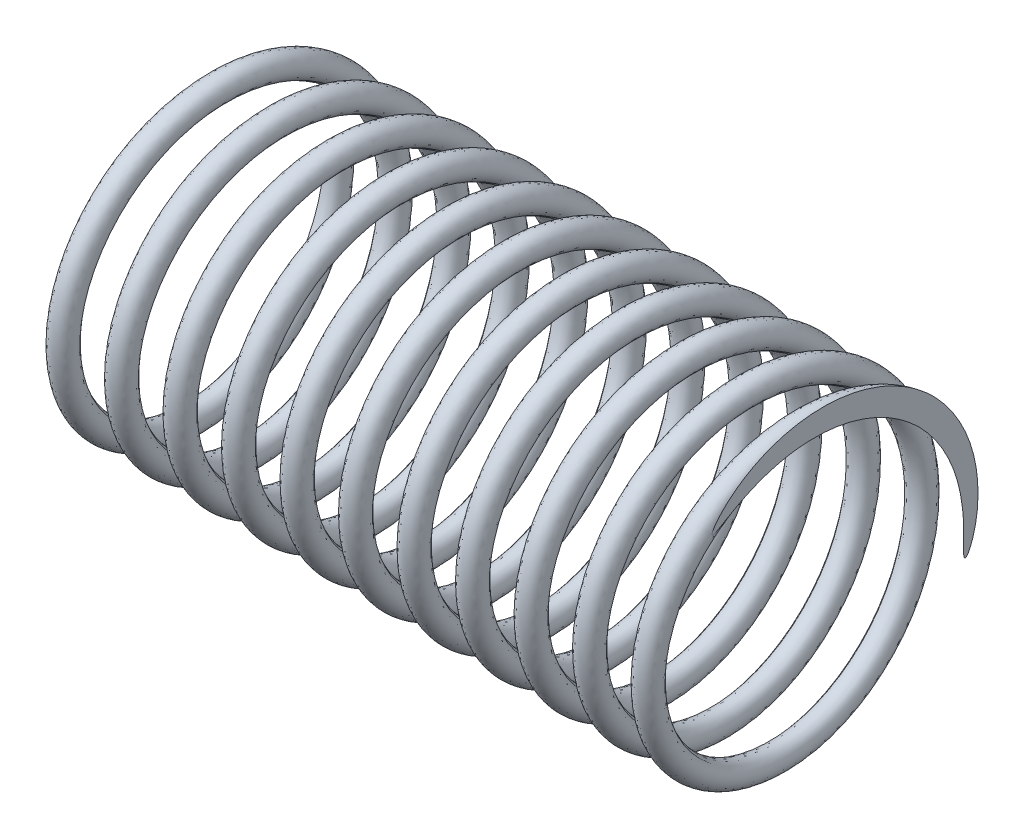
SolidWorks part; units mm, degrees
material "SPRING STEEL ASTM A 229"
ref_plane "Front Plane" through (0, 0, 0) normal (0, 0, 1) x (1, 0, 0)
ref_plane "Top Plane" through (0, 0, 0) normal (0, 1, 0) x (1, 0, 0)
ref_plane "Right Plane" through (0, 0, 0) normal (1, 0, 0) x (0, 0, -1)
sketch "Sketch1" plane through (0, 0, 0) normal (1, 0, 0) x (0, 0, -1)
  circle A0 centre (0, 0) radius 3.1
  dimension "D1" = 6.2
curve "Helix/Spiral1" pitch 1.2 height 26 radius 3.1 left hand yes centre (0, 0, 0) axis (1, 0, 0) start towards (0, 0, -1)
sketch "Sketch2" plane through (0, 0, 0) normal (0, 1, 0) x (1, 0, 0)
  circle A0 centre (0, 3.1) radius 0.25
  spline S0 degree 3 poles (0, 3.1) (0.0249, 3.1) (0.0752, 2.938) (0.1503, 2.2459) (0.2254, 1.2106) (0.3006, -0.0096) (0.3757, -1.2284) (0.4509, -2.2595) (0.526, -2.9453) (0.6012, -3.181) (0.6763, -2.9305) (0.7514, -2.2322) (0.8266, -1.1928) (0.9017, 0.0289) (0.9769, 1.2462) (1.052, 2.273) (1.1272, 2.9525) (1.2023, 3.1808) (1.2775, 2.923) (1.3526, 2.2185) (1.4277, 1.1749) (1.5029, -0.0481) (1.578, -1.2639) (1.6532, -2.2865) (1.7283, -2.9596) (1.8035, -3.1805) (1.8786, -2.9153) (1.9538, -2.2046) (2.0289, -1.157) (2.104, 0.0674) (2.1792, 1.2815) (2.2543, 2.2998) (2.3295, 2.9666) (2.4046, 3.1801) (2.4798, 2.9076) (2.5549, 2.1907) (2.6301, 1.1391) (2.7052, -0.0866) (2.7803, -1.2991) (2.8555, -2.3131) (2.9306, -2.9735) (3.0058, -3.1796) (3.0809, -2.8997) (3.1561, -2.1767) (3.2312, -1.1211) (3.3064, 0.1059) (3.3815, 1.3167) (3.4566, 2.3262) (3.5318, 2.9803) (3.6069, 3.1789) (3.6821, 2.8917) (3.7572, 2.1626) (3.8324, 1.103) (3.9075, -0.1251) (3.9827, -1.3342) (4.0578, -2.3393) (4.1329, -2.987) (4.2081, -3.1782) (4.2832, -2.8837) (4.3584, -2.1485) (4.4335, -1.085) (4.5087, 0.1444) (4.5838, 1.3516) (4.659, 2.3523) (4.7341, 2.9935) (4.8092, 3.1773) (4.8844, 2.8755) (4.9595, 2.1342) (5.0347, 1.0668) (5.1098, -0.1636) (5.185, -1.369) (5.2601, -2.3652) (5.3353, -3) (5.4104, -3.1763) (5.4855, -2.8672) (5.5607, -2.1199) (5.6358, -1.0487) (5.711, 0.1828) (5.7861, 1.3864) (5.8613, 2.3781) (5.9364, 3.0064) (6.0116, 3.1752) (6.0867, 2.8588) (6.1618, 2.1055) (6.237, 1.0305) (6.3121, -0.202) (6.3873, -1.4037) (6.4624, -2.3908) (6.5376, -3.0126) (6.6127, -3.174) (6.6879, -2.8503) (6.763, -2.0911) (6.8382, -1.0122) (6.9133, 0.2213) (6.9884, 1.4209) (7.0636, 2.4035) (7.1387, 3.0187) (7.2139, 3.1726) (7.289, 2.8417) (7.3642, 2.0765) (7.4393, 0.994) (7.5145, -0.2405) (7.5896, -1.4381) (7.6647, -2.4161) (7.7399, -3.0247) (7.815, -3.1712) (7.8902, -2.833) (7.9653, -2.0619) (8.0405, -0.9757) (8.1156, 0.2597) (8.1908, 1.4553) (8.2659, 2.4285) (8.341, 3.0306) (8.4162, 3.1696) (8.4913, 2.8242) (8.5665, 2.0472) (8.6416, 0.9573) (8.7168, -0.2788) (8.7919, -1.4724) (8.8671, -2.4409) (8.9422, -3.0364) (9.0173, -3.1679) (9.0925, -2.8153) (9.1676, -2.0324) (9.2428, -0.9389) (9.3179, 0.298) (9.3931, 1.4894) (9.4682, 2.4532) (9.5434, 3.0421) (9.6185, 3.1661) (9.6936, 2.8063) (9.7688, 2.0176) (9.8439, 0.9205) (9.9191, -0.3172) (9.9942, -1.5064) (10.0694, -2.4654) (10.1445, -3.0477) (10.2197, -3.1642) (10.2948, -2.7971) (10.3699, -2.0026) (10.4451, -0.9021) (10.5202, 0.3363) (10.5954, 1.5233) (10.6705, 2.4776) (10.7457, 3.0532) (10.8208, 3.1622) (10.896, 2.7879) (10.9711, 1.9876) (11.0462, 0.8836) (11.1214, -0.3555) (11.1965, -1.5402) (11.2717, -2.4896) (11.3468, -3.0585) (11.422, -3.16) (11.4971, -2.7786) (11.5723, -1.9726) (11.6474, -0.8651) (11.7225, 0.3746) (11.7977, 1.557) (11.8728, 2.5015) (11.948, 3.0637) (12.0231, 3.1577) (12.0983, 2.7692) (12.1734, 1.9574) (12.2486, 0.8465) (12.3237, -0.3937) (12.3988, -1.5738) (12.474, -2.5134) (12.5491, -3.0689) (12.6243, -3.1554) (12.6994, -2.7596) (12.7746, -1.9422) (12.8497, -0.828) (12.9249, 0.4128) (13, 1.5905) (13.0751, 2.5251) (13.1503, 3.0739) (13.2254, 3.1529) (13.3006, 2.75) (13.3757, 1.9269) (13.4509, 0.8094) (13.526, -0.4319) (13.6012, -1.6072) (13.6763, -2.5368) (13.7514, -3.0788) (13.8266, -3.1502) (13.9017, -2.7403) (13.9769, -1.9116) (14.052, -0.7907) (14.1272, 0.451) (14.2023, 1.6237) (14.2775, 2.5484) (14.3526, 3.0836) (14.4277, 3.1475) (14.5029, 2.7305) (14.578, 1.8961) (14.6532, 0.772) (14.7283, -0.47) (14.8035, -1.6403) (14.8786, -2.5599) (14.9538, -3.0882) (15.0289, -3.1447) (15.104, -2.7205) (15.1792, -1.8806) (15.2543, -0.7534) (15.3295, 0.4891) (15.4046, 1.6567) (15.4798, 2.5712) (15.5549, 3.0928) (15.6301, 3.1417) (15.7052, 2.7105) (15.7803, 1.8651) (15.8555, 0.7346) (15.9306, -0.5081) (16.0058, -1.6731) (16.0809, -2.5825) (16.1561, -3.0972) (16.2312, -3.1386) (16.3064, -2.7004) (16.3815, -1.8494) (16.4566, -0.7159) (16.5318, 0.5271) (16.6069, 1.6895) (16.6821, 2.5937) (16.7572, 3.1016) (16.8324, 3.1354) (16.9075, 2.6901) (16.9827, 1.8337) (17.0578, 0.6971) (17.1329, -0.5461) (17.2081, -1.7058) (17.2832, -2.6048) (17.3584, -3.1058) (17.4335, -3.1321) (17.5087, -2.6798) (17.5838, -1.818) (17.659, -0.6783) (17.7341, 0.565) (17.8092, 1.722) (17.8844, 2.6158) (17.9595, 3.1099) (18.0347, 3.1287) (18.1098, 2.6694) (18.185, 1.8021) (18.2601, 0.6595) (18.3353, -0.584) (18.4104, -1.7382) (18.4855, -2.6267) (18.5607, -3.1139) (18.6358, -3.1252) (18.711, -2.6589) (18.7861, -1.7862) (18.8613, -0.6406) (18.9364, 0.6029) (19.0116, 1.7543) (19.0867, 2.6375) (19.1618, 3.1178) (19.237, 3.1215) (19.3121, 2.6483) (19.3873, 1.7703) (19.4624, 0.6218) (19.5376, -0.6218) (19.6127, -1.7703) (19.6879, -2.6483) (19.763, -3.1215) (19.8382, -3.1178) (19.9133, -2.6375) (19.9884, -1.7543) (20.0636, -0.6029) (20.1387, 0.6406) (20.2139, 1.7862) (20.289, 2.6589) (20.3642, 3.1252) (20.4393, 3.1139) (20.5145, 2.6267) (20.5896, 1.7382) (20.6647, 0.584) (20.7399, -0.6595) (20.815, -1.8021) (20.8902, -2.6694) (20.9653, -3.1287) (21.0405, -3.1099) (21.1156, -2.6158) (21.1908, -1.722) (21.2659, -0.565) (21.341, 0.6783) (21.4162, 1.818) (21.4913, 2.6798) (21.5665, 3.1321) (21.6416, 3.1058) (21.7168, 2.6048) (21.7919, 1.7058) (21.8671, 0.5461) (21.9422, -0.6971) (22.0173, -1.8337) (22.0925, -2.6901) (22.1676, -3.1354) (22.2428, -3.1016) (22.3179, -2.5937) (22.3931, -1.6895) (22.4682, -0.5271) (22.5434, 0.7159) (22.6185, 1.8494) (22.6936, 2.7004) (22.7688, 3.1386) (22.8439, 3.0972) (22.9191, 2.5825) (22.9942, 1.6731) (23.0694, 0.5081) (23.1445, -0.7346) (23.2197, -1.8651) (23.2948, -2.7105) (23.3699, -3.1417) (23.4451, -3.0928) (23.5202, -2.5712) (23.5954, -1.6567) (23.6705, -0.4891) (23.7457, 0.7534) (23.8208, 1.8806) (23.896, 2.7205) (23.9711, 3.1447) (24.0462, 3.0882) (24.1214, 2.5599) (24.1965, 1.6403) (24.2717, 0.47) (24.3468, -0.772) (24.422, -1.8961) (24.4971, -2.7305) (24.5723, -3.1475) (24.6474, -3.0836) (24.7225, -2.5484) (24.7977, -1.6237) (24.8728, -0.451) (24.948, 0.7907) (25.0231, 1.9116) (25.0983, 2.7403) (25.1734, 3.1502) (25.2486, 3.0788) (25.3237, 2.5368) (25.3988, 1.6072) (25.474, 0.4319) (25.5491, -0.8093) (25.6243, -1.9269) (25.6994, -2.75) (25.7746, -3.1529) (25.8497, -3.0736) (25.9248, -2.5262) (25.9751, -1.8998) (26, -1.55) knots 0 0 0 0 0.00289 0.00578 0.008671 0.011561 0.014451 0.017341 0.020231 0.023121 0.026012 0.028902 0.031792 0.034682 0.037572 0.040462 0.043353 0.046243 0.049133 0.052023 0.054913 0.057803 0.060694 0.063584 0.066474 0.069364 0.072254 0.075145 0.078035 0.080925 0.083815 0.086705 0.089595 0.092486 0.095376 0.098266 0.101156 0.104046 0.106936 0.109827 0.112717 0.115607 0.118497 0.121387 0.124277 0.127168 0.130058 0.132948 0.135838 0.138728 0.141618 0.144509 0.147399 0.150289 0.153179 0.156069 0.15896 0.16185 0.16474 0.16763 0.17052 0.17341 0.176301 0.179191 0.182081 0.184971 0.187861 0.190751 0.193642 0.196532 0.199422 0.202312 0.205202 0.208092 0.210983 0.213873 0.216763 0.219653 0.222543 0.225434 0.228324 0.231214 0.234104 0.236994 0.239884 0.242775 0.245665 0.248555 0.251445 0.254335 0.257225 0.260116 0.263006 0.265896 0.268786 0.271676 0.274566 0.277457 0.280347 0.283237 0.286127 0.289017 0.291908 0.294798 0.297688 0.300578 0.303468 0.306358 0.309249 0.312139 0.315029 0.317919 0.320809 0.323699 0.32659 0.32948 0.33237 0.33526 0.33815 0.34104 0.343931 0.346821 0.349711 0.352601 0.355491 0.358382 0.361272 0.364162 0.367052 0.369942 0.372832 0.375723 0.378613 0.381503 0.384393 0.387283 0.390173 0.393064 0.395954 0.398844 0.401734 0.404624 0.407514 0.410405 0.413295 0.416185 0.419075 0.421965 0.424855 0.427746 0.430636 0.433526 0.436416 0.439306 0.442197 0.445087 0.447977 0.450867 0.453757 0.456647 0.459538 0.462428 0.465318 0.468208 0.471098 0.473988 0.476879 0.479769 0.482659 0.485549 0.488439 0.491329 0.49422 0.49711 0.5 0.50289 0.50578 0.508671 0.511561 0.514451 0.517341 0.520231 0.523121 0.526012 0.528902 0.531792 0.534682 0.537572 0.540462 0.543353 0.546243 0.549133 0.552023 0.554913 0.557803 0.560694 0.563584 0.566474 0.569364 0.572254 0.575145 0.578035 0.580925 0.583815 0.586705 0.589595 0.592486 0.595376 0.598266 0.601156 0.604046 0.606936 0.609827 0.612717 0.615607 0.618497 0.621387 0.624277 0.627168 0.630058 0.632948 0.635838 0.638728 0.641618 0.644509 0.647399 0.650289 0.653179 0.656069 0.65896 0.66185 0.66474 0.66763 0.67052 0.67341 0.676301 0.679191 0.682081 0.684971 0.687861 0.690751 0.693642 0.696532 0.699422 0.702312 0.705202 0.708092 0.710983 0.713873 0.716763 0.719653 0.722543 0.725434 0.728324 0.731214 0.734104 0.736994 0.739884 0.742775 0.745665 0.748555 0.751445 0.754335 0.757225 0.760116 0.763006 0.765896 0.768786 0.771676 0.774566 0.777457 0.780347 0.783237 0.786127 0.789017 0.791908 0.794798 0.797688 0.800578 0.803468 0.806358 0.809249 0.812139 0.815029 0.817919 0.820809 0.823699 0.82659 0.82948 0.83237 0.83526 0.83815 0.84104 0.843931 0.846821 0.849711 0.852601 0.855491 0.858382 0.861272 0.864162 0.867052 0.869942 0.872832 0.875723 0.878613 0.881503 0.884393 0.887283 0.890173 0.893064 0.895954 0.898844 0.901734 0.904624 0.907514 0.910405 0.913295 0.916185 0.919075 0.921965 0.924855 0.927746 0.930636 0.933526 0.936416 0.939306 0.942197 0.945087 0.947977 0.950867 0.953757 0.956647 0.959538 0.962428 0.965318 0.968208 0.971098 0.973988 0.976879 0.979769 0.982659 0.985549 0.988439 0.991329 0.99422 0.99711 1 1 1 1 construction
  dimension "D1" = 0.5
sweep "Sweep1" add profiles "Sketch2" path "Helix/Spiral1"
sketch "Sketch3" plane through (0, 0, 0) normal (0, 0, 1) x (1, 0, 0)
  line L0 (0, 0) -> (28.1754, 0) construction
  line L1 (58, 6.4802) -> (13, 6.4802)
  line L2 (58, 6.4802) -> (58, -6.4802)
  line L3 (58, -6.4802) -> (13, -6.4802)
  line L4 (13, 6.4802) -> (13, -6.4802)
  line L5 (0, 4.7829) -> (-1.4284, 4.7829)
  line L6 (0, 4.7829) -> (0, -6.4802)
  line L7 (0, -6.4802) -> (-1.4284, -6.4802)
  line L8 (-1.4284, 4.7829) -> (-1.4284, -6.4802)
  dimension "D1" = 11.2631
  dimension "D2" = 1.4284
  dimension "D3" = 4.7829
  dimension "D4" = 45
  dimension "D5" = 13
  dimension "D6" = 12.9605
extrude "Cut-Extrude1" cut sketch "Sketch3" against normal through all and the other way through all
ref_axis "Axis1" through (-1.7699, 0, 0) along (1, 0, 0)
